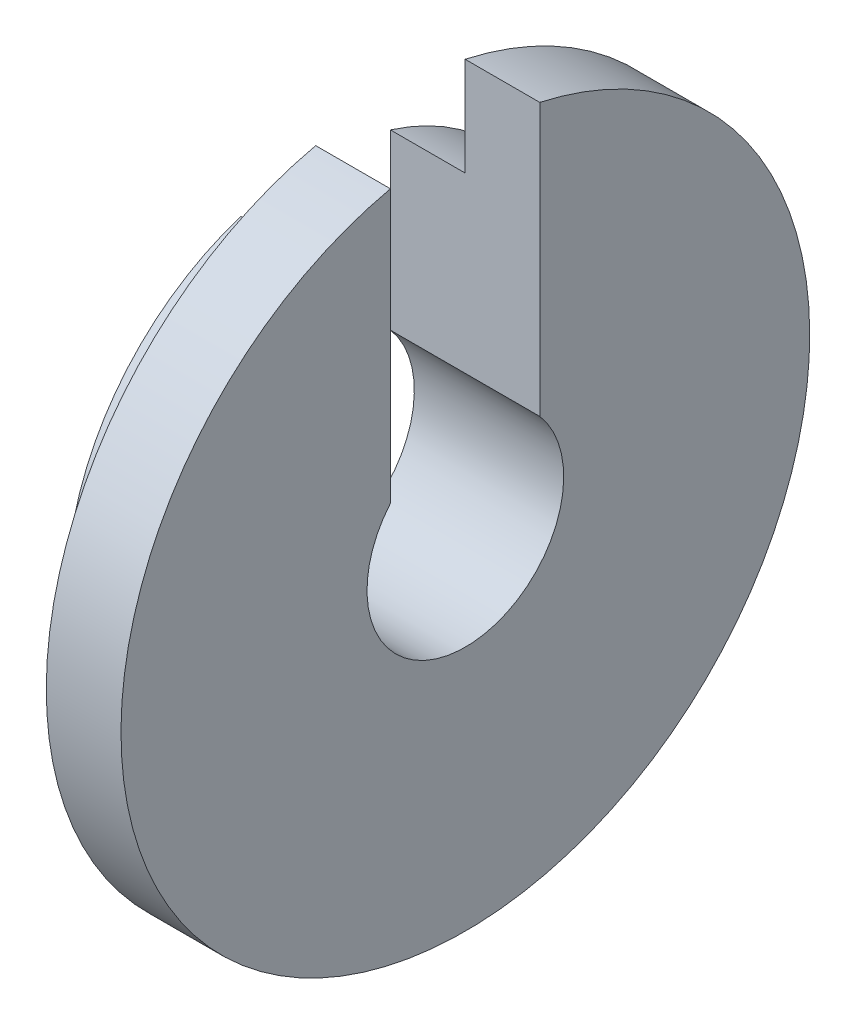
SolidWorks part; units mm, degrees
ref_plane "Front Plane" through (0, 0, 0) normal (0, 0, 1) x (1, 0, 0)
ref_plane "Top Plane" through (0, 0, 0) normal (0, 1, 0) x (1, 0, 0)
ref_plane "Right Plane" through (0, 0, 0) normal (1, 0, 0) x (0, 0, -1)
sketch "Sketch1" plane through (0, 0, 0) normal (1, 0, 0) x (0, 0, -1)
  line L2 (0.7593, 3.4301) -> (0.7593, 0.6558)
  line L4 (-0.7647, 3.4289) -> (-0.7647, 0.6495)
  arc A0 (-0.7647, 0.6495) -> (0.7593, 0.6558) centre (0, 0) ccw
  arc A1 (-0.7647, 3.4289) -> (0.7593, 3.4301) centre (0, 0) ccw
  point P1 (0, 0)
  point P3 (0, 0)
  point P4 (-0.0027, 2.8539)
  point P6 (0, 0)
  point P8 (0, 0)
  point P11 (0, 0)
  point P12 (0, 0)
  point P13 (0, 0)
  point P14 (0, 0)
  point P15 (0, 0)
  dimension "D1" = 1.524
  dimension "D2" = 1.0033
  dimension "D3" = 0.762
extrude "Boss-Extrude1" add sketch "Sketch1" along normal blind 0.762
sketch "Sketch3" plane through (0.762, 0, 0) normal (1, 0, 0) x (0, 0, -1)
  line L0 (-0.7647, 2.4233) -> (-0.7647, 0.6495)
  line L1 (-0.7647, 0.6495) -> (-0.7647, 3.4289) construction
  line L2 (0.7593, 2.425) -> (0.7593, 0.6558)
  line L3 (0.7593, 3.4301) -> (0.7593, 0.6558) construction
  arc A0 (-0.7647, 2.4233) -> (0.7593, 2.425) centre (0, 0) ccw
  arc A1 (-0.7647, 0.6495) -> (0.7593, 0.6558) centre (0, 0) ccw
extrude "Boss-Extrude2" add sketch "Sketch3" against normal blind 1.524
